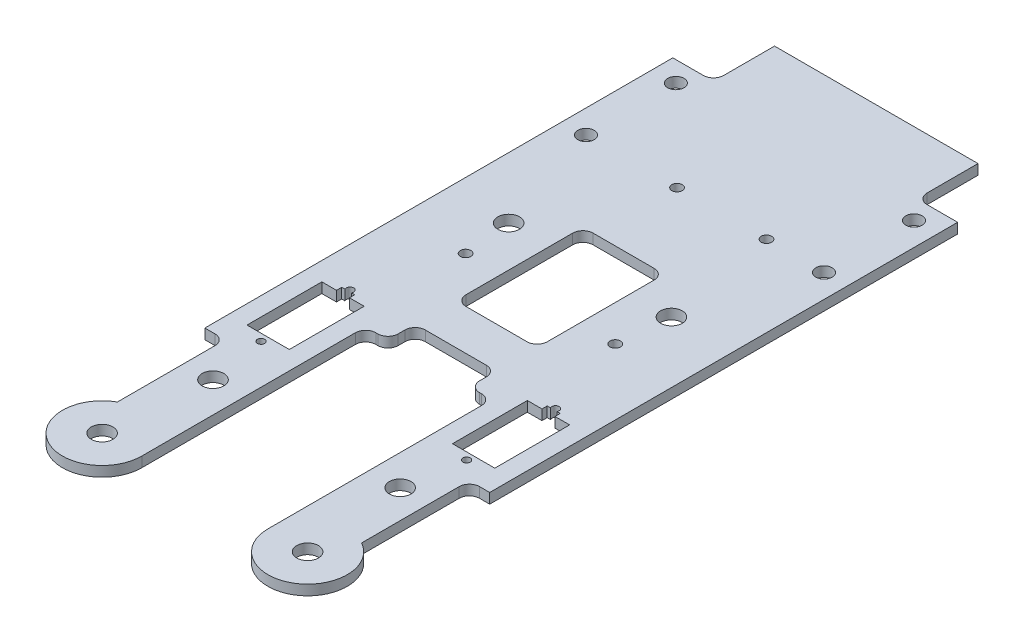
SolidWorks part; units mm, degrees
material "6061-T4 (SS)"
ref_plane "Front Plane" through (0, 0, 0) normal (0, 0, 1) x (1, 0, 0)
ref_plane "Top Plane" through (0, 0, 0) normal (0, 1, 0) x (1, 0, 0)
ref_plane "Right Plane" through (0, 0, 0) normal (1, 0, 0) x (0, 0, -1)
sketch "Sketch1" plane through (0, 0, 0) normal (0, 1, 0) x (1, 0, 0)
  line L1 (-44.45, -114.3) -> (44.45, -114.3)
  line L2 (-44.45, -114.3) -> (-44.45, 114.3)
  line L3 (-44.45, 114.3) -> (44.45, 114.3)
  line L4 (44.45, -114.3) -> (44.45, 114.3)
  line L5 (-44.45, -114.3) -> (44.45, 114.3) construction
  line L6 (-44.45, 114.3) -> (44.45, -114.3) construction
  point P0 (0, 0)
  dimension "D1" = 88.9
  dimension "D2" = 228.6
extrude "Boss-Extrude1" add sketch "Sketch1" along normal blind 3.175
sketch "Sketch11" plane through (0, 3.175, 0) normal (0, 1, 0) x (1, 0, 0)
  line L0 (0, 31.75) -> (97.4414, 31.75) construction
  line L10 (0, 0) -> (0, 114.3) construction
  line L14 (44.45, 114.3) -> (-44.45, 114.3) construction
  line L15 (0, 0) -> (117.475, 0) construction
  circle A0 centre (-26.289, 4.9828) radius 1.25
  circle A1 centre (-25.019, 53.1832) radius 1.25
  circle A2 centre (25.781, 38.1972) radius 1.25
  circle A3 centre (25.781, 10.0628) radius 1.25
  dimension "D3" = 2.5
  dimension "D5" = 2.5
  dimension "D7" = 31.75
  dimension "D9" = 25.781
  dimension "D4" = 2.5
  dimension "D6" = 2.5
  dimension "D2" = 25.019
  dimension "D8" = 26.289
  dimension "D10" = 6.4472
  dimension "D11" = 25.781
  dimension "D12" = 21.6872
  dimension "D13" = 26.7672
  dimension "D14" = 21.4332
extrude "Cut-Extrude12" [suppressed] cut sketch "Sketch11" against normal through all
sketch "Sketch18" plane through (0, 3.175, 0) normal (0, 1, 0) x (1, 0, 0)
  line L0 (44.45, 79.883) -> (-44.45, 79.883) construction
  line L1 (44.45, -114.3) -> (44.45, 114.3) construction
  line L2 (-44.45, 114.3) -> (-44.45, -114.3) construction
  line L3 (44.45, 114.3) -> (-44.45, 114.3) construction
  line L4 (0, 79.883) -> (0, -114.3) construction
  line L5 (-44.45, -114.3) -> (44.45, -114.3) construction
  circle A9 centre (-23.9014, 29.083) radius 1.632
  circle A10 centre (23.9014, 27.9832) radius 1.632
  circle A11 centre (-8.702, 79.883) radius 1.6319
  circle A12 centre (19.1999, 79.883) radius 1.6319
  dimension "D4" = 50.8
  dimension "D9" = 15.1994
  dimension "D11" = 3.2639
  dimension "D13" = 43.1013
  dimension "D3" = 3.2639
  dimension "D2" = 3.2639
  dimension "D8" = 3.2639
  dimension "D1" = 34.417
  dimension "D5" = 23.9014
  dimension "D6" = 47.8028
  dimension "D7" = 1.0998
  dimension "D10" = 50.8
  dimension "D12" = 50.8
sketch "Sketch12" plane through (0, 3.175, 0) normal (0, 1, 0) x (1, 0, 0)
  line L0 (0, 0) -> (44.45, 0) construction
  line L1 (44.45, -114.3) -> (44.45, 114.3) construction
  line L2 (0, 0) -> (0, 114.3) construction
  line L3 (44.45, 114.3) -> (-44.45, 114.3) construction
  line L4 (44.45, -44.45) -> (-44.45, -44.45) construction
  line L5 (-19.685, -69.85) -> (19.685, -69.85)
  line L6 (-19.685, -69.85) -> (-19.685, -6.35)
  line L7 (-19.685, -6.35) -> (19.685, -6.35)
  line L8 (19.685, -69.85) -> (19.685, -6.35)
  line L9 (-19.685, -69.85) -> (19.685, -6.35) construction
  line L10 (-19.685, -6.35) -> (19.685, -69.85) construction
  line L11 (-44.45, 114.3) -> (-44.45, -114.3) construction
  line L12 (0, -38.1) -> (0, -114.3) construction
  line L13 (-44.45, -114.3) -> (44.45, -114.3) construction
  circle A0 centre (29.21, -44.45) radius 3.3782
  circle A1 centre (-29.21, -44.45) radius 3.3782
  point P5 (0, -38.1)
  dimension "D5" = 6.7564
  dimension "D1" = 63.5
  dimension "D2" = 38.1
  dimension "D3" = 39.37
  dimension "D4" = 25.4
  dimension "D6" = 58.42
extrude "Cut-Extrude13" cut sketch "Sketch12" against normal through all
sketch "Sketch14" plane through (0, 0, 0) normal (0, -1, 0) x (-1, 0, 0)
  line L0 (0, 114.3) -> (0, 31.056) construction
  line L1 (-44.45, 114.3) -> (44.45, 114.3) construction
  line L2 (0, 114.3) -> (-44.45, 114.3) construction
  line L3 (-41.91, 114.3) -> (-41.91, 67.4804) construction
  line L5 (-32.385, 114.3) -> (-32.385, 67.4804) construction
  line L6 (-32.385, 107.95) -> (-41.91, 107.95) construction
  line L7 (-32.385, 93.9165) -> (-41.91, 93.9165) construction
  line L8 (-44.45, -114.3) -> (-44.45, 114.3) construction
  circle A0 centre (-37.1475, 107.95) radius 2.5527
  circle A1 centre (-37.1475, 79.883) radius 2.5527
  circle A2 centre (37.1475, 107.95) radius 2.5527
  circle A3 centre (37.1475, 79.883) radius 2.5527
  dimension "D4" = 5.1054
  dimension "D1" = 2.54
  dimension "D2" = 9.525
  dimension "D3" = 6.35
  dimension "D5" = 14.0335
extrude "Cut-Extrude15" cut sketch "Sketch14" against normal through all
sketch "Sketch15" plane through (0, 0, 0) normal (0, -1, 0) x (1, 0, 0)
  line L0 (44.45, 114.3) -> (44.45, -114.3) construction
  line L1 (-44.45, 114.3) -> (44.45, 114.3)
  line L2 (-44.45, 114.3) -> (-44.45, 57.15)
  line L3 (-44.45, 57.15) -> (44.45, 57.15)
  line L4 (44.45, 114.3) -> (44.45, 57.15)
  line L5 (19.685, 6.35) -> (-19.685, 6.35) construction
  line L6 (0, -24.0665) -> (0, -114.3) construction
  line L7 (12.7, -51.308) -> (12.7, -17.9917)
  line L8 (9.525, -14.8167) -> (-9.525, -14.8167)
  line L9 (44.45, -114.3) -> (-44.45, -114.3) construction
  line L10 (-12.7, -17.9917) -> (-12.7, -51.308)
  line L11 (9.525, -54.483) -> (-9.525, -54.483)
  line L12 (12.7, -51.308) -> (12.7, 6.35) construction
  line L13 (12.7, 6.35) -> (-12.7, 6.35) construction
  line L14 (-12.7, -51.308) -> (-12.7, 6.35) construction
  line L15 (12.7, -54.483) -> (-12.7, 6.35) construction
  line L16 (12.7, 6.35) -> (-12.7, -54.483) construction
  line L17 (12.7, 6.35) -> (-12.7, 6.35)
  line L18 (-12.7, 6.35) -> (-12.7, 1.0583)
  line L19 (-9.525, -2.1167) -> (9.525, -2.1167)
  line L20 (12.7, 1.0583) -> (12.7, 6.35)
  circle A0 centre (-29.21, 44.45) radius 3.3782 construction
  circle A1 centre (-37.1475, -79.883) radius 2.5527 construction
  arc A2 (-9.525, -54.483) -> (-12.7, -51.308) centre (-9.525, -51.308) cw
  arc A3 (9.525, -54.483) -> (12.7, -51.308) centre (9.525, -51.308) ccw
  arc A4 (12.7, -17.9917) -> (9.525, -14.8167) centre (9.525, -17.9917) ccw
  arc A5 (-9.525, -14.8167) -> (-12.7, -17.9917) centre (-9.525, -17.9917) ccw
  arc A6 (-12.7, 1.0583) -> (-9.525, -2.1167) centre (-9.525, 1.0583) ccw
  arc A7 (9.525, -2.1167) -> (12.7, 1.0583) centre (9.525, 1.0583) ccw
  point P35 (12.7, -14.8167)
  point P38 (-12.7, -14.8167)
  point P41 (-12.7, -2.1167)
  point P44 (12.7, -2.1167)
  dimension "D3" = 3.175
  dimension "D7" = 3.175
  dimension "D1" = 12.7
  dimension "D2" = 25.4
  dimension "D4" = 25.4
  dimension "D5" = 8.4667
  dimension "D6" = 12.7
extrude "Cut-Extrude16" cut sketch "Sketch15" against normal through all
fillet "Fillet1" radius 3.175 4 edges at (19.685, 1.5875, 6.35) (-19.685, 1.5875, 6.35) (-12.7, 1.5875, 6.35) (12.7, 1.5875, 6.35)
extrude "Cut-Extrude18" cut sketch "Sketch18" against normal through all
sketch "Sketch16" plane through (0, 3.175, 0) normal (0, 1, 0) x (1, 0, 0)
  line L0 (44.45, -57.15) -> (44.45, -76.2)
  line L1 (19.685, -57.15) -> (19.685, -76.2)
  line L2 (19.685, -76.2) -> (44.45, -76.2) construction
  line L3 (0, 0) -> (0, -94.827) construction
  line L4 (44.45, -57.15) -> (19.685, -57.15)
  line L5 (-19.685, -57.15) -> (-19.685, -76.2)
  line L6 (-44.45, -57.15) -> (-19.685, -57.15)
  line L7 (-44.45, -57.15) -> (-44.45, -76.2)
  arc A0 (44.45, -76.2) -> (19.685, -76.2) centre (32.0675, -76.2) cw
  arc A1 (-44.45, -76.2) -> (-19.685, -76.2) centre (-32.0675, -76.2) ccw
  circle A2 centre (32.0675, -76.2) radius 3.3782
  circle A3 centre (-32.0675, -76.2) radius 3.3782
  line M12 (-44.45, -57.15) -> (-19.685, -57.15)
  line M16 (19.685, -57.15) -> (44.45, -57.15)
  dimension "D2" = 6.7564
  dimension "D1" = 19.05
extrude "Boss-Extrude2" add sketch "Sketch16" against normal up to surface (3.175 mm away) contours L7 A1 L5 A3 M12 | A0 L0 L1 A2 M16 region at (32.0675, 3.175, 71.4304) region at (-32.0675, 3.175, 71.4304) up to face at (23.9014, 0, -26.3512)
sketch "Sketch17" plane through (0, 3.175, 0) normal (0, 1, 0) x (1, 0, 0)
  line L0 (38.1, -65.3863) -> (38.1, -34.925)
  line L1 (44.45, -76.2) -> (44.45, 114.3) construction
  line L9 (0, 0) -> (0, -71.3802) construction
  line L15 (41.275, -31.75) -> (44.45, -31.75)
  line L20 (44.45, -31.75) -> (44.45, -76.2)
  line L21 (-41.275, -31.75) -> (-44.45, -31.75)
  line L22 (-38.1, -65.3863) -> (-38.1, -34.925)
  line L23 (-44.45, -31.75) -> (-44.45, -76.2)
  circle A4 centre (32.0675, -76.2) radius 3.3046 construction
  arc A5 (38.1, -34.925) -> (41.275, -31.75) centre (41.275, -34.925) cw
  circle A10 centre (32.0675, -76.2) radius 12.3825 construction
  arc A11 (38.1, -65.3863) -> (44.45, -76.2) centre (32.0675, -76.2) cw
  arc A12 (-38.1, -34.925) -> (-41.275, -31.75) centre (-41.275, -34.925) ccw
  arc A13 (-38.1, -65.3863) -> (-44.45, -76.2) centre (-32.0675, -76.2) ccw
  point P11 (38.1, -31.75)
  dimension "D2" = 3.175
  dimension "D3" = 44.45
  dimension "D1" = 6.35
extrude "Cut-Extrude17" cut sketch "Sketch17" against normal through all
sketch "Sketch19" plane through (0, 3.175, 0) normal (0, 1, 0) x (1, 0, 0)
  line L0 (0, 14.8167) -> (0, 54.483) construction
  line L1 (9.525, 14.8167) -> (-9.525, 14.8167) construction
  line L2 (-9.525, 54.483) -> (9.525, 54.483) construction
  line L4 (-12.7, 17.9917) -> (-12.7, 51.308) construction
  line L6 (-38.1, 53.975) -> (-12.7, 53.975) construction
  line L7 (-25.4, 53.975) -> (-25.4, 44.0267) construction
  line L9 (-44.45, 114.3) -> (-44.45, -31.75) construction
  circle A0 centre (-25.4, 44.0267) radius 3.3782
  circle A1 centre (25.4, 44.0267) radius 3.3782
  dimension "D1" = 6.7564
  dimension "D2" = 29.21
  dimension "D3" = 6.35
extrude "Cut-Extrude19" cut sketch "Sketch19" against normal through all
sketch "Sketch20" plane through (0, 3.175, 0) normal (0, 1, 0) x (1, 0, 0)
  line L0 (0, 0) -> (0, 61.1006) construction
  line L3 (-25.8445, 3.175) -> (-25.8445, -28.575) construction
  line L6 (-25.4635, -1.016) -> (-38.6715, -1.016) construction
  line L7 (-25.4635, -1.016) -> (-25.4635, -24.384)
  line L8 (-25.4635, -24.384) -> (-38.6715, -24.384)
  line L9 (-38.6715, -1.016) -> (-38.6715, -24.384)
  line L10 (-25.4635, -1.016) -> (-38.6715, -24.384) construction
  line L11 (-25.4635, -24.384) -> (-38.6715, -1.016) construction
  line L13 (-38.2905, 3.175) -> (-38.2905, -28.575) construction
  line L14 (-25.8445, 3.175) -> (-38.2905, -28.575) construction
  line L27 (-32.0675, -76.2) -> (-32.0675, 23.1424) construction
  line L28 (-38.2905, 3.175) -> (-25.8445, -28.575) construction
  line L29 (-38.2905, -28.575) -> (-32.9565, -28.575) construction
  line L30 (-32.9565, -28.575) -> (-32.9565, -27.305) construction
  line L31 (-31.1785, -28.575) -> (-31.1785, -27.305) construction
  line L32 (-25.8445, -28.575) -> (-31.1785, -28.575) construction
  line L33 (-25.8445, 3.175) -> (-31.1785, 3.175) construction
  line L34 (-31.1785, 3.175) -> (-31.1785, 1.905) construction
  line L35 (-32.9565, 3.175) -> (-32.9565, 1.905) construction
  line L36 (-38.2905, 3.175) -> (-32.9565, 3.175) construction
  line L38 (-30.0355, -1.016) -> (-30.0355, 0.6151)
  line L42 (-30.0355, -1.016) -> (-25.4635, -1.016)
  line L44 (-34.0995, -1.016) -> (-34.0995, 0.6151)
  line L45 (-34.0995, -1.016) -> (-38.6715, -1.016)
  line L47 (-33.0574, 0.6151) -> (-34.0995, 0.6151)
  line L48 (-32.0675, 1.1866) -> (-32.0675, 0.0436) construction
  line L49 (-32.0675, 1.1866) -> (-32.0675, 0.0436) construction
  line L50 (-32.0675, 0.6151) -> (-30.8266, 0.6151) construction
  line L51 (-30.0355, 0.6151) -> (-31.0776, 0.6151)
  line L52 (30.0355, -1.016) -> (30.0355, 0.6151)
  line L53 (30.0355, -1.016) -> (25.4635, -1.016)
  line L54 (25.4635, -1.016) -> (25.4635, -24.384)
  line L55 (25.4635, -24.384) -> (38.6715, -24.384)
  line L56 (38.6715, -1.016) -> (38.6715, -24.384)
  line L57 (34.0995, -1.016) -> (38.6715, -1.016)
  line L58 (34.0995, -1.016) -> (34.0995, 0.6151)
  line L59 (33.0574, 0.6151) -> (34.0995, 0.6151)
  line L60 (30.0355, 0.6151) -> (31.0776, 0.6151)
  arc A0 (-32.9565, -27.305) -> (-31.1785, -27.305) centre (-32.0675, -26.5866) cw construction
  arc A1 (-32.9565, 1.905) -> (-31.1785, 1.905) centre (-32.0675, 1.1866) ccw construction
  circle A2 centre (-32.0675, 1.1866) radius 1.143 construction
  circle A3 centre (-32.0675, -26.5866) radius 1.143
  circle A4 centre (32.0675, -26.5866) radius 1.143
  arc A7 (-33.0574, 0.6151) -> (-31.0776, 0.6151) centre (-32.0675, 1.1866) cw
  arc A8 (33.0574, 0.6151) -> (31.0776, 0.6151) centre (32.0675, 1.1866) ccw
  point P10 (-32.0675, -12.7)
  point P16 (-32.0675, -12.7)
  dimension "D1" = 13.208
  dimension "D2" = 23.368
  dimension "D3" = 63.5
  dimension "D4" = 2.032
extrude "Cut-Extrude20" cut sketch "Sketch20" against normal through all
sketch "Sketch21" plane through (0, 0, -114.3) normal (0, 0, -1) x (-1, 0, 0)
  line L1 (44.45, 0) -> (-44.45, 0)
  line L2 (44.45, 0) -> (44.45, 3.175)
  line L3 (44.45, 3.175) -> (-44.45, 3.175)
  line L4 (-44.45, 0) -> (-44.45, 3.175)
extrude "Boss-Extrude3" add sketch "Sketch21" along normal blind 19.05
sketch "Sketch22" plane through (0, 3.175, 0) normal (0, 1, 0) x (1, 0, 0)
  line L0 (0, 54.483) -> (0, 133.35) construction
  line L1 (-44.45, 133.35) -> (-31.75, 133.35)
  line L2 (-44.45, 133.35) -> (-44.45, 114.3)
  line L3 (-44.45, 114.3) -> (-34.925, 114.3)
  line L4 (-31.75, 133.35) -> (-31.75, 117.475)
  line L5 (-9.525, 54.483) -> (9.525, 54.483) construction
  line L6 (44.45, 133.35) -> (-44.45, 133.35) construction
  line L7 (44.45, 114.3) -> (34.925, 114.3)
  line L8 (31.75, 133.35) -> (31.75, 117.475)
  line L9 (44.45, 133.35) -> (31.75, 133.35)
  line L10 (44.45, 133.35) -> (44.45, 114.3)
  arc A0 (-34.925, 114.3) -> (-31.75, 117.475) centre (-34.925, 117.475) ccw
  arc A1 (34.925, 114.3) -> (31.75, 117.475) centre (34.925, 117.475) cw
  point P13 (-31.75, 114.3)
  dimension "D3" = 3.175
  dimension "D1" = 12.7
  dimension "D2" = 19.05
extrude "Cut-Extrude21" cut sketch "Sketch22" against normal through all
